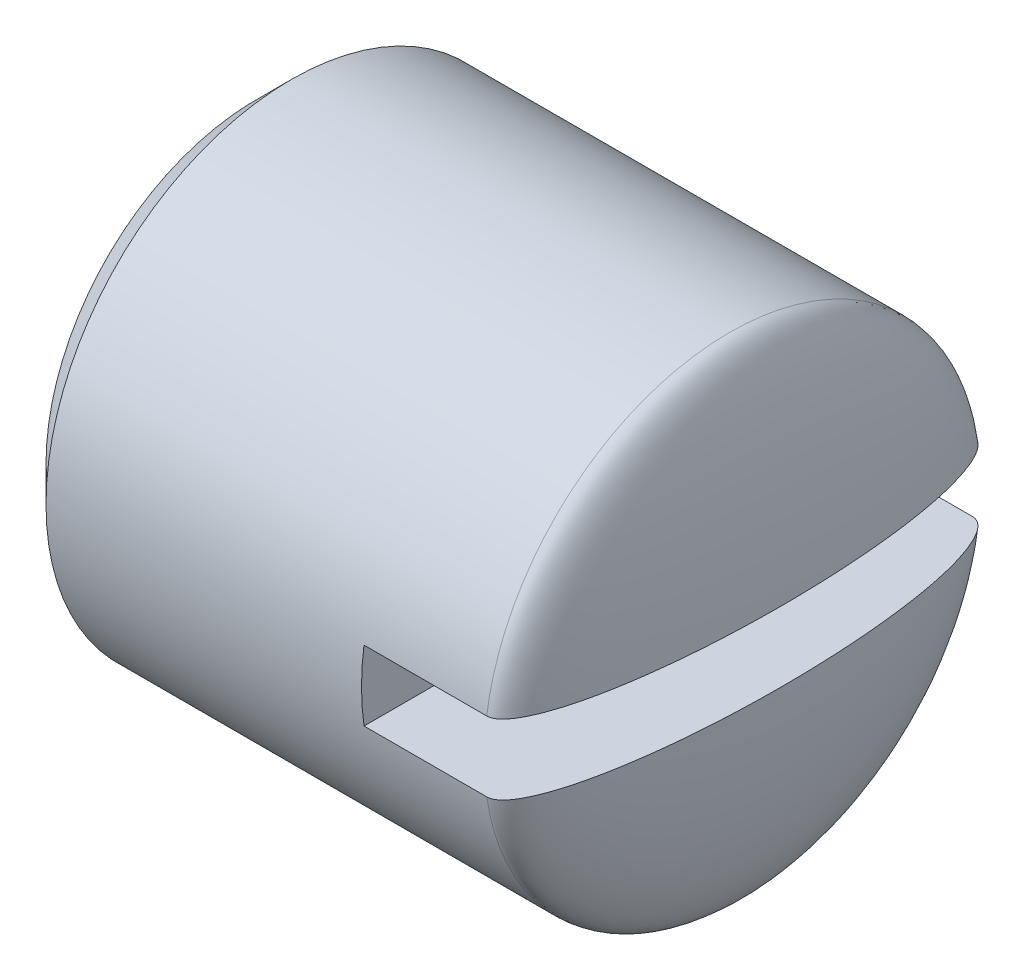
SolidWorks part; units mm, degrees
ref_plane "Front Plane" through (0, 0, 0) normal (0, 0, 1) x (1, 0, 0)
ref_plane "Top Plane" through (0, 0, 0) normal (0, 1, 0) x (1, 0, 0)
ref_plane "Right Plane" through (0, 0, 0) normal (1, 0, 0) x (0, 0, -1)
sketch "Sketch1" plane through (0, 0, 0) normal (1, 0, 0) x (0, 0, -1)
  circle A0 centre (0, 0) radius 7
extrude "Boss-Extrude1" add sketch "Sketch1" against normal blind 15
cosmetic thread "Cosmetic Thread1" parameters "D1"=5, "D2"=12.344
chamfer "Chamfer1" distance 1 angle 45 1 edges at (-15, 0, -7)
fillet "Fillet1" radius 6.99 1 edges at (0, 0, -7) second distance 1.5 first distance on face at (0, 0, -7)
sketch "Sketch3" plane through (0, 0, 0) normal (0, 0, 1) x (1, 0, 0)
  line L1 (0, 0.99) -> (-5, 0.99)
  line L2 (0, -1.01) -> (-5, -1.01)
  line L3 (-5, 0.99) -> (-5, -1.01)
  line L4 (0, 0.99) -> (0, -1.01)
extrude "Cut-Extrude1" cut sketch "Sketch3" against normal through all both and the other way through all
